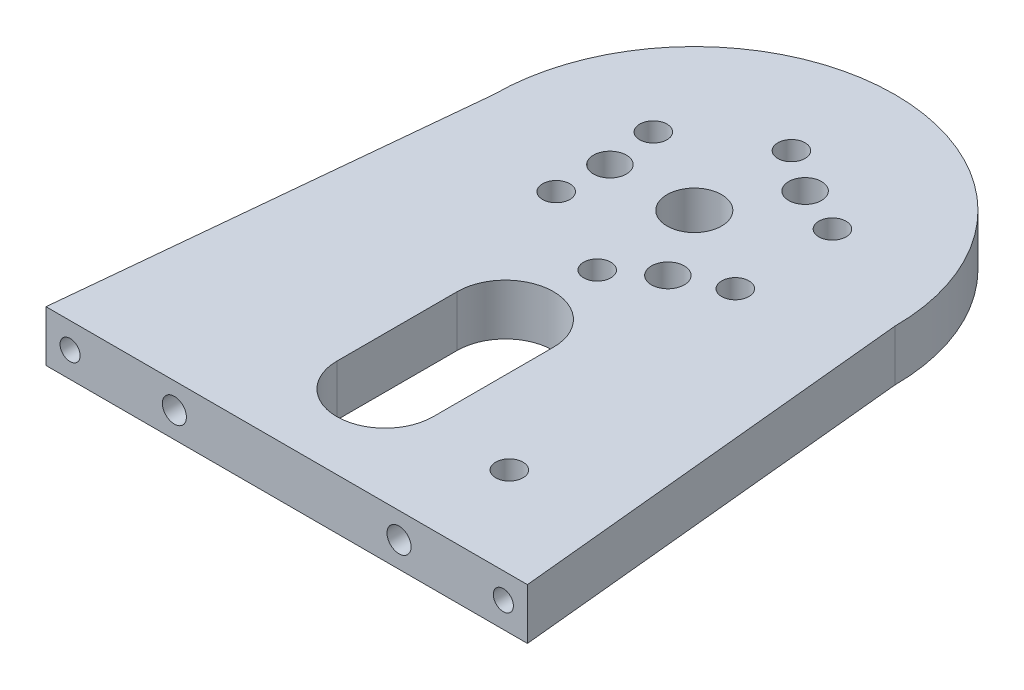
SolidWorks part; units mm, degrees
material "Aleación 6061"
ref_plane "Alzado" through (0, 0, 0) normal (0, 0, 1) x (1, 0, 0)
ref_plane "Planta" through (0, 0, 0) normal (0, 1, 0) x (1, 0, 0)
ref_plane "Vista lateral" through (0, 0, 0) normal (1, 0, 0) x (0, 0, -1)
ref_plane "Plano_zJ2" through (0, 0, 171.45) normal (0, 0, 1) x (1, 0, 0)
ref_plane "Plano_xJ3" through (152.4, 0, 0) normal (1, 0, 0) x (0, 0, -1)
ref_axis "Eje_J3" through (152.4, -33, 171.45) along (0, 1, 0)
ref_axis "Eje_J4" through (152.4, 0, 226.04) along (0, 0, -1)
sketch "Croquis12" plane through (0, 0, 0) normal (0, 1, 0) x (1, 0, 0)
  line L0 (127.4, -171.45) -> (177.4, -171.45)
  line L1 (177.4, -171.45) -> (182.4, -222.25)
  line L2 (182.4, -222.25) -> (122.4, -222.25)
  line L3 (122.4, -222.25) -> (127.4, -171.45)
  dimension "D1" = 127.4
  dimension "D2" = 171.45
  dimension "D3" = 177.4
  dimension "D4" = 171.45
  dimension "D5" = 182.4
  dimension "D6" = 222.25
  dimension "D7" = 122.4
  dimension "D8" = 222.25
extrude "Placa_antebrazo" add sketch "Croquis12" along normal blind 6.35 from offset 3.175 offset against normal yes
sketch "Croquis13" plane through (0, 0, 0) normal (0, 1, 0) x (1, 0, 0)
  circle A0 centre (152.4, -171.45) radius 25
  dimension "D1" = 50
  dimension "D2" = 152.4
  dimension "D3" = 171.45
extrude "Placa_antebrazo_redondeo" add sketch "Croquis13" along normal blind 6.35 from offset 3.175 offset against normal yes
sketch "Croquis14" plane through (0, 0, 0) normal (0, 1, 0) x (1, 0, 0)
  circle A0 centre (163.4163, -177.3569) radius 1.7
  circle A1 centre (152.7926, -183.9438) radius 1.7
  circle A2 centre (141.7763, -178.0369) radius 1.7
  circle A3 centre (141.3837, -165.5431) radius 1.7
  circle A4 centre (152.0074, -158.9562) radius 1.7
  circle A5 centre (163.0237, -164.8631) radius 1.7
  circle A6 centre (157.7749, -180.1189) radius 2.05
  circle A7 centre (142.205, -171.7704) radius 2.05
  circle A8 centre (157.22, -162.4607) radius 2.05
  circle A9 centre (152.4, -171.45) radius 3.4
  dimension "D1" = 3.4
  dimension "D2" = 3.4
  dimension "D3" = 3.4
  dimension "D4" = 3.4
  dimension "D5" = 3.4
  dimension "D6" = 3.4
  dimension "D7" = 4.1
  dimension "D8" = 4.1
  dimension "D9" = 4.1
  dimension "D10" = 6.8
  dimension "D11" = 163.4163
  dimension "D12" = 177.3569
  dimension "D13" = 152.7926
  dimension "D14" = 183.9438
  dimension "D15" = 141.7763
  dimension "D16" = 178.0369
  dimension "D17" = 141.3837
  dimension "D18" = 165.5431
  dimension "D19" = 152.0074
  dimension "D20" = 158.9562
  dimension "D21" = 163.0237
  dimension "D22" = 164.8631
  dimension "D23" = 157.7749
  dimension "D24" = 180.1189
  dimension "D25" = 142.205
  dimension "D26" = 171.7704
  dimension "D27" = 157.22
  dimension "D28" = 162.4607
  dimension "D29" = 152.4
  dimension "D30" = 171.45
extrude "Barrenos_J3" cut sketch "Croquis14" along normal blind 6.35 from offset 3.175 offset against normal yes
sketch "Croquis15" plane through (0, 0, 0) normal (0, 1, 0) x (1, 0, 0)
  circle A0 centre (163.4163, -177.3569) radius 3
  circle A1 centre (152.7926, -183.9438) radius 3
  circle A2 centre (141.7763, -178.0369) radius 3
  circle A3 centre (141.3837, -165.5431) radius 3
  circle A4 centre (152.0074, -158.9562) radius 3
  circle A5 centre (163.0237, -164.8631) radius 3
  dimension "D1" = 6
  dimension "D2" = 6
  dimension "D3" = 6
  dimension "D4" = 6
  dimension "D5" = 6
  dimension "D6" = 6
  dimension "D7" = 163.4163
  dimension "D8" = 177.3569
  dimension "D9" = 152.7926
  dimension "D10" = 183.9438
  dimension "D11" = 141.7763
  dimension "D12" = 178.0369
  dimension "D13" = 141.3837
  dimension "D14" = 165.5431
  dimension "D15" = 152.0074
  dimension "D16" = 158.9562
  dimension "D17" = 163.0237
  dimension "D18" = 164.8631
extrude "Refrentados_J3" cut sketch "Croquis15" along normal blind 3.2 from offset 3.175 offset against normal yes
sketch "Croquis16" plane through (0, 0, 0) normal (0, 1, 0) x (1, 0, 0)
  line L0 (158.4, -195) -> (158.4, -210)
  line L1 (146.4, -210) -> (146.4, -195)
  arc A0 (158.4, -210) -> (146.4, -210) centre (152.4, -210) cw
  arc A1 (146.4, -195) -> (158.4, -195) centre (152.4, -195) cw
  dimension "D1" = 6
  dimension "D2" = 6
  dimension "D3" = 158.4
  dimension "D4" = 195
  dimension "D5" = 158.4
  dimension "D6" = 210
  dimension "D7" = 146.4
  dimension "D8" = 210
  dimension "D9" = 146.4
  dimension "D10" = 195
extrude "Aligerado_paso_cable" cut sketch "Croquis16" along normal blind 6.35 from offset 3.175 offset against normal yes
sketch "Croquis17" plane through (0, 0, 0) normal (0, 0, 1) x (1, 0, 0)
  circle A0 centre (125.4, 0) radius 1.25
  circle A1 centre (179.4, 0) radius 1.25
  dimension "D1" = 2.5
  dimension "D2" = 2.5
  dimension "D3" = 125.4
  dimension "D4" = 179.4
extrude "Rosca_M3_canto" cut sketch "Croquis17" along normal blind 9 from offset 213.25
sketch "Croquis18" plane through (0, 0, 0) normal (0, 0, 1) x (1, 0, 0)
  circle A0 centre (138.4, 0) radius 1.5
  circle A1 centre (166.4, 0) radius 1.5
  dimension "D1" = 3
  dimension "D2" = 3
  dimension "D3" = 138.4
  dimension "D4" = 166.4
extrude "Pasadores_D3" cut sketch "Croquis18" along normal blind 7 from offset 215.25
sketch "Croquis19" plane through (0, 0, 0) normal (0, 1, 0) x (1, 0, 0)
  circle A0 centre (171.4, -211) radius 1.25
  circle A1 centre (166.4, -211) radius 1.25
  dimension "D1" = 2.5
  dimension "D2" = 2.5
  dimension "D3" = 171.4
  dimension "D4" = 211
  dimension "D5" = 166.4
  dimension "D6" = 211
sketch "Croquis20" plane through (0, 0, 0) normal (0, 1, 0) x (1, 0, 0)
  circle A0 centre (168.9, -211) radius 1.7
  dimension "D1" = 3.4
  dimension "D2" = 168.9
  dimension "D3" = 211
extrude "Paso_M3_bases_cincho" cut sketch "Croquis20" along normal blind 6.35 from offset 3.175 offset against normal yes
